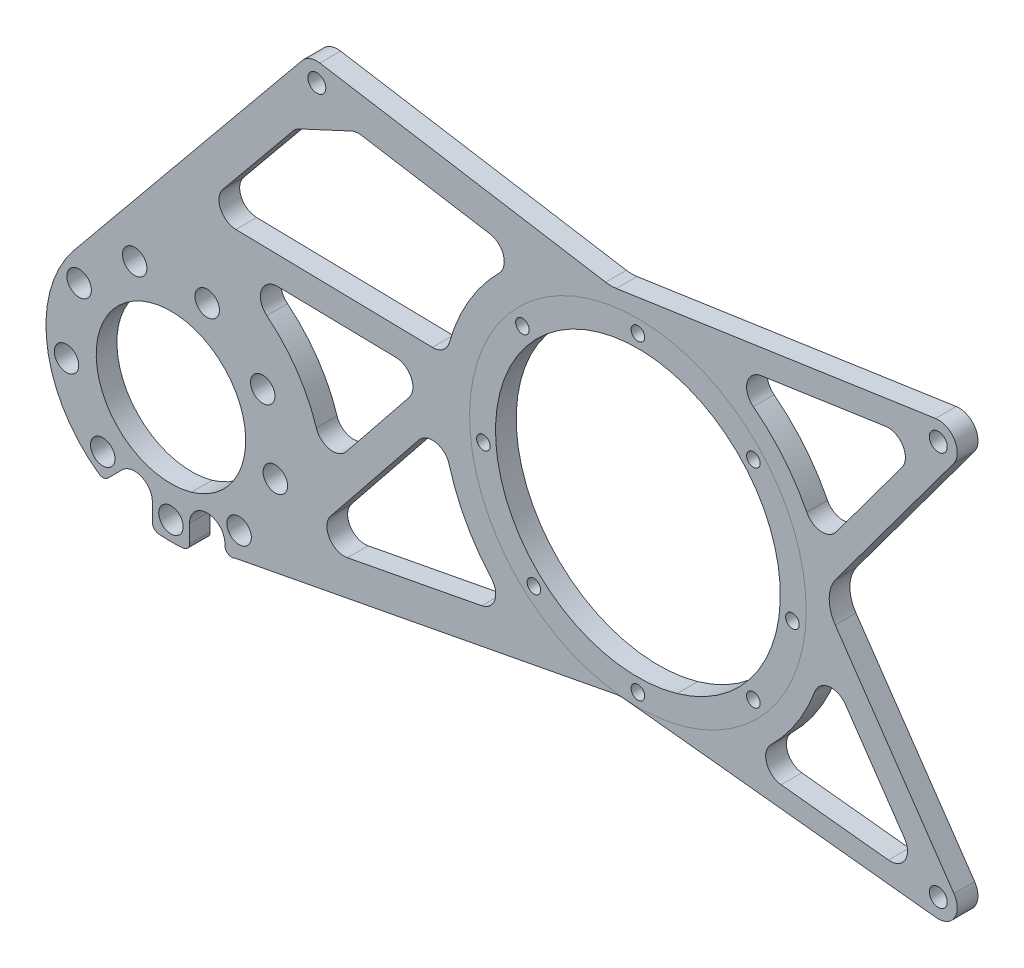
SolidWorks part; units mm, degrees
material "6061-T6 (SS)"
ref_plane "X-Y Datum" through (0, 0, 0) normal (0, 0, 1) x (1, 0, 0)
ref_plane "X-Z Datum" through (0, 0, 0) normal (0, 1, 0) x (1, 0, 0)
ref_plane "Y-Z Datum" through (0, 0, 0) normal (1, 0, 0) x (0, 0, -1)
sketch "Sketch15" plane through (0, 0, 0) normal (0, 0, 1) x (-1, 0, 0)
  line L0 (-666.75, 77.9015) -> (-548.64, 0) construction
  line L1 (-666.75, 77.9015) -> (-494.9785, 127) construction
  line L8 (-471.7786, 164.3167) -> (-477.0435, 159.0518)
  line L9 (-488.1397, 163.648) -> (-488.1397, 170.2207)
  line L10 (-501.8173, 170.2207) -> (-501.8173, 163.648)
  line L11 (-514.8173, 163.648) -> (-514.8173, 164.225)
  line L17 (-660.4, 0) -> (-548.64, 0)
  line L18 (-777.24, 0) -> (-660.4, 0)
  line L19 (-777.24, 145.034) -> (-777.24, 0)
  line L20 (-789.94, 132.334) -> (-764.54, 157.734)
  line L21 (-789.94, 157.734) -> (-764.54, 132.334)
  line L22 (-789.94, 132.334) -> (-764.54, 132.334)
  line L23 (-789.94, 157.734) -> (-764.54, 157.734)
  line L24 (-789.94, 157.734) -> (-789.94, 132.334)
  line L25 (-764.54, 157.734) -> (-764.54, 132.334)
  line L26 (-543.2372, -4.4272) -> (-459.4185, 97.8608)
  line L27 (-777.24, -6.985) -> (-548.64, -6.985)
  line L28 (-784.225, 0) -> (-784.225, 145.034)
  line L29 (-776.4928, 151.9789) -> (-660.1268, 139.4587)
  line L30 (-660.1268, 139.4587) -> (-518.666, 166.4019)
  circle A1 centre (-666.75, 77.9015) radius 52.3875
  circle A4 centre (-548.64, 0) radius 12.7
  circle A5 centre (-777.24, 0) radius 12.7
  arc A16 (-518.666, 166.4019) -> (-468.5208, 164.5979) centre (-494.9785, 127) ccw
  arc A17 (-468.5208, 164.5979) -> (-471.7786, 164.3167) centre (-469.9826, 162.5207) ccw
  arc A18 (-488.1397, 163.648) -> (-477.0435, 159.0518) centre (-481.6397, 163.648) ccw
  arc A19 (-488.1397, 170.2207) -> (-490.4283, 172.7483) centre (-490.6797, 170.2207) ccw
  arc A20 (-490.4283, 172.7483) -> (-499.5287, 172.7483) centre (-494.9785, 127) ccw
  arc A21 (-499.5287, 172.7483) -> (-501.8173, 170.2207) centre (-499.2773, 170.2207) ccw
  arc A22 (-514.8173, 163.648) -> (-501.8173, 163.648) centre (-508.3173, 163.648) ccw
  arc A23 (-514.8173, 164.225) -> (-518.666, 166.4019) centre (-517.3573, 164.225) ccw
  circle A30 centre (-709.2207, 116.1423) radius 2.5
  circle A31 centre (-624.2793, 39.6607) radius 2.5
  circle A33 centre (-709.2207, 39.6607) radius 2.5
  circle A34 centre (-723.5869, 83.8753) radius 2.5
  circle A35 centre (-609.9131, 83.8753) radius 2.5
  circle A36 centre (-666.75, 20.7515) radius 2.5
  arc A40 (-666.75, 132.5515) -> (-666.75, 137.5515) centre (-666.75, 135.0515) ccw
  arc A41 (-666.75, 137.5515) -> (-666.75, 132.5515) centre (-666.75, 135.0515) ccw
  circle A43 centre (-628.5092, 120.3722) radius 2.5
  circle A45 centre (-666.75, 77.9015) radius 61.9125
  circle A46 centre (-548.64, 0) radius 3.3
  circle A47 centre (-777.24, 0) radius 3.3
  circle A48 centre (-777.24, 145.034) radius 3.3
  circle A49 centre (-548.64, 0) radius 6.985
  circle A50 centre (-777.24, 0) radius 6.985
  circle A51 centre (-777.24, 145.034) radius 6.985
  circle A61 centre (-461.2035, 107.5) radius 4.5
  circle A62 centre (-481.6397, 90.352) radius 4.5
  circle A63 centre (-508.3173, 90.352) radius 4.5
  circle A64 centre (-528.7535, 107.5) radius 4.5
  circle A65 centre (-533.386, 133.7723) radius 4.5
  circle A66 centre (-520.0472, 156.8757) radius 4.5
  circle A67 centre (-494.9785, 166) radius 4.5
  circle A68 centre (-469.9098, 156.8757) radius 4.5
  circle A69 centre (-456.571, 133.7723) radius 4.5
  circle A71 centre (-494.9785, 127) radius 27.4955
  dimension "D2" = 6.6
  dimension "D3" = 6.6
  dimension "D4" = 6.6
  dimension "D5" = 13.97
  dimension "D6" = 13.97
  dimension "D7" = 13.97
  dimension "D1" = 141.4871
extrude "Boss-Extrude1" add sketch "Sketch15" along normal blind 7.62 contours A45 A1 A30 A31 A33 A34 A35 A36 A41 A40 A43 | L30 A45 L29 L25 L22 L19 A5 L18 L17 A4 L26 A16 | A51 L21 L25 L29 L20 | A51 L19 L22 L21 | L19 A51 L21 A48 | L20 A51 L19 A48 | A51 L28 L20 | A51 L20 L28 L22 L19 | L21 A51 L20 A48 | A51 L20 A48 L21 | L20 A51 L21 A48 | A51 L20 L29 | A5 L19 L22 L28 | A50 L19 A5 L28 | A50 L18 A5 L19 | A50 L27 A5 L18 | A50 L18 A47 L19 | L18 A50 L19 A47 | A5 L27 A4 L17 L18 | A49 L17 A4 L27 | A49 L26 A4 L17 | A49 A46 | L11 A23 A16 A17 L8 A18 L9 A19 A20 A21 L10 A22 A71 A69 A68 A67 A66 A65 A64 A63 A62 A61 region at (470.0892, -163.7557, 0) region at (621.9919, -118.1022, 0) region at (500.7414, -53.0926, 0) region at (540.1092, 0.1341, 0) region at (545.7357, 6.1347, 0) region at (662.94, 3.5042, 0) region at (557.2397, 3.7525, 0) region at (767.6155, -143.202, 0) region at (768.6403, 3.7525, 0) region at (770.798, -6.442, 0) region at (772.2286, -135.2354, 0) region at (772.7928, -151.1055, 0) region at (782.0394, 4.7994, 0) region at (780.9925, -8.5997, 0) region at (780.7424, -72.1789, 0) region at (773.8261, -3.4139, 0) region at (775.2402, -140.206, 0) region at (772.412, -145.034, 0) region at (780.8486, -135.5958, 0) region at (777.24, -149.862, 0) region at (782.068, -145.034, 0) region at (779.2398, -140.206, 0) region at (783.5955, -140.54, 0)
ref_point "Point1"
ref_point "Point2"
ref_plane "Plane1" through (666.75, -77.9015, 0) normal (-0.9615, -0.2748, 0) x (0, 0, 1)
ref_plane "Plane2" through (494.9785, -127, 0) normal (0.9615, 0.2748, 0) x (0, 0, -1)
split line "Split Line1"
split line "Split Line2"
sketch "Sketch17" plane through (0, 0, 7.62) normal (0, 0, 1) x (1, 0, 0)
  circle A0 centre (666.75, -77.9015) radius 61.9125 construction
  circle A1 centre (666.75, -77.9015) radius 61.9125
split line "Split Line3"
ref_axis "Axis4" through (666.75, -77.9015, 7.62) along (0, 0, -1)
ref_axis "Axis5" through (494.9785, -127, 7.62) along (0, 0, -1)
sketch "Sketch18" plane through (0, 0, 7.62) normal (0, 0, 1) x (1, 0, 0)
  line L4 (514.8173, -163.648) -> (514.8173, -164.225)
  line L5 (501.8173, -170.2207) -> (501.8173, -163.648)
  line L6 (488.1397, -163.648) -> (488.1397, -170.2207)
  line L7 (471.7786, -164.3167) -> (477.0435, -159.0518)
  line L8 (514.8173, -163.648) -> (514.8173, -164.225)
  line L9 (501.8173, -170.2207) -> (501.8173, -163.648)
  line L10 (488.1397, -163.648) -> (488.1397, -170.2207)
  line L11 (471.7786, -164.3167) -> (477.0435, -159.0518)
  line L12 (734.2162, -69.8493) -> (782.8538, -4.1564)
  line L13 (734.2162, -69.8493) -> (783.0031, -141.0872)
  line L14 (776.2216, 6.9104) -> (656.8438, -10.6825)
  line L15 (656.8438, -10.6825) -> (549.7714, 6.8928)
  line L16 (776.4928, -151.9789) -> (687.9549, -142.4528)
  line L17 (776.4928, -151.9789) -> (660.1268, -139.4587) construction
  line L18 (543.2372, 4.4272) -> (459.4185, -97.8608) construction
  line L19 (543.2372, 4.4272) -> (459.4185, -97.8608)
  line L20 (660.1268, -139.4587) -> (518.666, -166.4019) construction
  line L21 (660.1268, -139.4587) -> (518.666, -166.4019)
  circle A0 centre (666.75, -77.9015) radius 67.945
  circle A1 centre (666.75, -77.9015) radius 52.3875
  circle A2 centre (666.75, -77.9015) radius 52.3875
  circle A3 centre (548.64, 0) radius 12.7
  circle A4 centre (548.64, 0) radius 12.7
  circle A5 centre (777.24, 0) radius 12.7
  circle A6 centre (777.24, 0) radius 12.7
  circle A7 centre (777.24, 0) radius 6.985 construction
  circle A8 centre (777.24, -145.034) radius 6.985 construction
  circle A9 centre (548.64, 0) radius 6.985 construction
  arc A10 (514.8173, -164.225) -> (518.666, -166.4019) centre (517.3573, -164.225) ccw
  arc A11 (514.8173, -163.648) -> (501.8173, -163.648) centre (508.3173, -163.648) ccw
  arc A12 (499.5287, -172.7483) -> (501.8173, -170.2207) centre (499.2773, -170.2207) ccw
  arc A13 (490.4283, -172.7483) -> (499.5287, -172.7483) centre (494.9785, -127) ccw
  arc A14 (488.1397, -170.2207) -> (490.4283, -172.7483) centre (490.6797, -170.2207) ccw
  arc A15 (488.1397, -163.648) -> (477.0435, -159.0518) centre (481.6397, -163.648) ccw
  arc A16 (468.5208, -164.5979) -> (471.7786, -164.3167) centre (469.9826, -162.5207) ccw
  arc A17 (518.666, -166.4019) -> (468.5208, -164.5979) centre (494.9785, -127) ccw
  arc A18 (514.8173, -164.225) -> (518.666, -166.4019) centre (517.3573, -164.225) ccw
  arc A19 (514.8173, -163.648) -> (501.8173, -163.648) centre (508.3173, -163.648) ccw
  arc A20 (499.5287, -172.7483) -> (501.8173, -170.2207) centre (499.2773, -170.2207) ccw
  arc A21 (490.4283, -172.7483) -> (499.5287, -172.7483) centre (494.9785, -127) ccw
  arc A22 (488.1397, -170.2207) -> (490.4283, -172.7483) centre (490.6797, -170.2207) ccw
  arc A23 (488.1397, -163.648) -> (477.0435, -159.0518) centre (481.6397, -163.648) ccw
  arc A24 (468.5208, -164.5979) -> (471.7786, -164.3167) centre (469.9826, -162.5207) ccw
  arc A25 (518.666, -166.4019) -> (468.5208, -164.5979) centre (494.9785, -127) ccw
  circle A26 centre (777.24, -145.034) radius 6.985
  circle A27 centre (777.24, 0) radius 6.985
  circle A28 centre (548.64, 0) radius 6.985
  line M37 (784.225, -145.034) -> (784.225, 0)
  line M39 (777.24, 6.985) -> (548.64, 6.985)
  dimension "D5" = 135.89
  dimension "D6" = 65.6929
  dimension "D1" = 0
  dimension "D2" = 0
  dimension "D3" = 0
  dimension "D4" = 0
extrude "Profile" cut sketch "Sketch18" against normal through all contours A6 A4 L15 L14 M39 | A28 L15 A4 M39 | A27 A6 L14 M39 | A26 A6 L12 L13 M37 | A27 L12 A6 M37 region at (660.9586, 1.0495, 7.62) region at (769.684, 6.4437, 7.62) region at (556.2469, 6.3803, 7.62) region at (767.4156, -72.3216, 7.62) region at (781.5837, -8.7535, 7.62)
fillet "Prof Fillet" radius 12.7 3 edges at (660.1268, -139.4587, 3.81) (734.2162, -69.8493, 3.81) (656.8438, -10.6825, 3.81)
sketch "Sketch19" plane through (0, 0, 7.62) normal (0, 0, 1) x (1, 0, 0)
  line L0 (732.9468, -56.6236) -> (772.9791, -2.5535)
  line L1 (772.9791, -2.5535) -> (694.453, -14.126)
  line L2 (776.2216, 6.9104) -> (658.8007, -10.3941) construction
  line L3 (739.5986, -62.5794) -> (782.8538, -4.1564) construction
  line L4 (514.8173, -163.648) -> (514.8173, -164.225)
  line L5 (501.8173, -170.2207) -> (501.8173, -163.648)
  line L6 (488.1397, -163.648) -> (488.1397, -170.2207)
  line L7 (471.7786, -164.3167) -> (477.0435, -159.0518)
  line L8 (514.8173, -163.648) -> (514.8173, -164.225)
  line L9 (501.8173, -170.2207) -> (501.8173, -163.648)
  line L10 (488.1397, -163.648) -> (488.1397, -170.2207)
  line L11 (471.7786, -164.3167) -> (477.0435, -159.0518)
  line L12 (735.3185, -89.4398) -> (772.6135, -143.8976)
  line L13 (772.6135, -143.8976) -> (704.1334, -136.5295)
  line L14 (739.3273, -77.3124) -> (783.0031, -141.0872) construction
  line L15 (776.4928, -151.9789) -> (660.1268, -139.4587) construction
  arc A0 (694.453, -14.126) -> (732.9468, -56.6236) centre (666.75, -77.9015) cw
  circle A1 centre (666.75, -77.9015) radius 52.3875
  circle A2 centre (666.75, -77.9015) radius 52.3875
  circle A3 centre (548.64, 0) radius 12.7
  circle A4 centre (548.64, 0) radius 12.7
  circle A5 centre (777.24, 0) radius 12.7
  circle A6 centre (777.24, 0) radius 12.7
  circle A7 centre (666.75, -77.9015) radius 61.9125 construction
  arc A8 (704.1334, -136.5295) -> (735.3185, -89.4398) centre (666.75, -77.9015) ccw
  arc A10 (514.8173, -164.225) -> (518.666, -166.4019) centre (517.3573, -164.225) ccw
  arc A11 (514.8173, -163.648) -> (501.8173, -163.648) centre (508.3173, -163.648) ccw
  arc A12 (499.5287, -172.7483) -> (501.8173, -170.2207) centre (499.2773, -170.2207) ccw
  arc A13 (490.4283, -172.7483) -> (499.5287, -172.7483) centre (494.9785, -127) ccw
  arc A14 (488.1397, -170.2207) -> (490.4283, -172.7483) centre (490.6797, -170.2207) ccw
  arc A15 (488.1397, -163.648) -> (477.0435, -159.0518) centre (481.6397, -163.648) ccw
  arc A16 (468.5208, -164.5979) -> (471.7786, -164.3167) centre (469.9826, -162.5207) ccw
  arc A17 (518.666, -166.4019) -> (468.5208, -164.5979) centre (494.9785, -127) ccw
  arc A18 (514.8173, -164.225) -> (518.666, -166.4019) centre (517.3573, -164.225) ccw
  arc A19 (514.8173, -163.648) -> (501.8173, -163.648) centre (508.3173, -163.648) ccw
  arc A20 (499.5287, -172.7483) -> (501.8173, -170.2207) centre (499.2773, -170.2207) ccw
  arc A21 (490.4283, -172.7483) -> (499.5287, -172.7483) centre (494.9785, -127) ccw
  arc A22 (488.1397, -170.2207) -> (490.4283, -172.7483) centre (490.6797, -170.2207) ccw
  arc A23 (488.1397, -163.648) -> (477.0435, -159.0518) centre (481.6397, -163.648) ccw
  arc A24 (468.5208, -164.5979) -> (471.7786, -164.3167) centre (469.9826, -162.5207) ccw
  arc A25 (518.666, -166.4019) -> (468.5208, -164.5979) centre (494.9785, -127) ccw
  dimension "D7" = 7.62
  dimension "D8" = 7.62
  dimension "D5" = 8.89
  dimension "D6" = 8.89
  dimension "D9" = 10.16
  dimension "D10" = 7.62
  dimension "D1" = 0
  dimension "D2" = 0
  dimension "D3" = 0
  dimension "D4" = 0
extrude "Cut-Extrude2" cut sketch "Sketch19" against normal through all contours L1 A0 L0 | A8 L13 L12 | L1 A6 L0 | L13 A8 L12 region at (735.5667, -23.3598, 7.62) region at (768.629, -5.1605, 7.62) region at (739.7271, -124.6517, 7.62)
fillet "Fillet2" radius 6.35 6 edges at (694.453, -14.126, 3.81) (772.9791, -2.5535, 3.81) (732.9468, -56.6236, 3.81) (772.6135, -143.8976, 3.81) (704.1334, -136.5295, 3.81) (735.3185, -89.4398, 3.81)
sketch "Sketch22" plane through (0, 0, 7.62) normal (0, 0, 1) x (1, 0, 0)
  line L0 (625.9593, -18.4829) -> (563.0994, -8.1649)
  line L1 (563.0994, -8.1649) -> (540.883, -18.4829)
  line L2 (654.892, -10.3621) -> (549.7714, 6.8928) construction
  line L4 (514.8173, -163.648) -> (514.8173, -164.225)
  line L5 (501.8173, -170.2207) -> (501.8173, -163.648)
  line L6 (488.1397, -163.648) -> (488.1397, -170.2207)
  line L7 (471.7786, -164.3167) -> (477.0435, -159.0518)
  line L8 (514.8173, -163.648) -> (514.8173, -164.225)
  line L9 (501.8173, -170.2207) -> (501.8173, -163.648)
  line L10 (488.1397, -163.648) -> (488.1397, -170.2207)
  line L11 (471.7786, -164.3167) -> (477.0435, -159.0518)
  line L12 (621.3887, -133.9086) -> (542.9827, -148.8422)
  line L13 (542.9827, -148.8422) -> (594.9409, -84.0572)
  line L14 (658.2707, -139.8122) -> (518.666, -166.4019) construction
  line L15 (505.7956, -61.3018) -> (540.883, -18.4829)
  line L16 (540.883, -18.4829) -> (625.9593, -18.4829)
  line L17 (596.2144, -63.0967) -> (505.7956, -61.3018)
  line L18 (543.2372, 4.4272) -> (459.4185, -97.8608) construction
  line L19 (502.7234, -71.4029) -> (590.6658, -73.1486)
  line L20 (590.6658, -73.1486) -> (550.9456, -122.6744)
  arc A0 (594.9409, -84.0572) -> (621.3887, -133.9086) centre (666.75, -77.9015) ccw
  circle A1 centre (666.75, -77.9015) radius 52.3875
  circle A2 centre (666.75, -77.9015) radius 52.3875
  circle A3 centre (548.64, 0) radius 12.7
  circle A4 centre (548.64, 0) radius 12.7
  circle A5 centre (777.24, 0) radius 12.7
  circle A6 centre (777.24, 0) radius 12.7
  circle A7 centre (666.75, -77.9015) radius 61.9125 construction
  arc A8 (625.9593, -18.4829) -> (596.2144, -63.0967) centre (666.75, -77.9015) ccw
  arc A9 (502.7234, -71.4029) -> (550.9456, -122.6744) centre (494.9785, -127) cw
  arc A10 (514.8173, -164.225) -> (518.666, -166.4019) centre (517.3573, -164.225) ccw
  arc A11 (514.8173, -163.648) -> (501.8173, -163.648) centre (508.3173, -163.648) ccw
  arc A12 (499.5287, -172.7483) -> (501.8173, -170.2207) centre (499.2773, -170.2207) ccw
  arc A13 (490.4283, -172.7483) -> (499.5287, -172.7483) centre (494.9785, -127) ccw
  arc A14 (488.1397, -170.2207) -> (490.4283, -172.7483) centre (490.6797, -170.2207) ccw
  arc A15 (488.1397, -163.648) -> (477.0435, -159.0518) centre (481.6397, -163.648) ccw
  arc A16 (468.5208, -164.5979) -> (471.7786, -164.3167) centre (469.9826, -162.5207) ccw
  arc A17 (518.666, -166.4019) -> (468.5208, -164.5979) centre (494.9785, -127) ccw
  arc A18 (514.8173, -164.225) -> (518.666, -166.4019) centre (517.3573, -164.225) ccw
  arc A19 (514.8173, -163.648) -> (501.8173, -163.648) centre (508.3173, -163.648) ccw
  arc A20 (499.5287, -172.7483) -> (501.8173, -170.2207) centre (499.2773, -170.2207) ccw
  arc A21 (490.4283, -172.7483) -> (499.5287, -172.7483) centre (494.9785, -127) ccw
  arc A22 (488.1397, -170.2207) -> (490.4283, -172.7483) centre (490.6797, -170.2207) ccw
  arc A23 (488.1397, -163.648) -> (477.0435, -159.0518) centre (481.6397, -163.648) ccw
  arc A24 (468.5208, -164.5979) -> (471.7786, -164.3167) centre (469.9826, -162.5207) ccw
  arc A25 (518.666, -166.4019) -> (468.5208, -164.5979) centre (494.9785, -127) ccw
  dimension "D6" = 10.16
  dimension "D7" = 10.16
  dimension "D14" = 10.16
  dimension "D5" = 12.7
  dimension "D8" = 12.7
  dimension "D9" = 12.7
  dimension "D10" = 24.4955
  dimension "D11" = 90.4189
  dimension "D12" = 51.9581
  dimension "D13" = 64.7849
  dimension "D15" = 10.16
  dimension "D16" = 10.16
  dimension "D17" = 1.7949
  dimension "D1" = 0
  dimension "D2" = 0
  dimension "D3" = 0
  dimension "D4" = 0
extrude "Cut-Extrude4" cut sketch "Sketch22" against normal through all contours L1 L16 L0 | L17 L15 L16 A8 | L20 A9 L19 | L13 A0 L12 region at (576.6473, -15.0436, 7.62)
fillet "Fillet5" radius 6.35 11 edges at (621.3887, -133.9086, 3.81) (542.9827, -148.8422, 3.81) (594.9409, -84.0572, 3.81) (550.9456, -122.6744, 3.81) (590.6658, -73.1486, 3.81) (502.7234, -71.4029, 3.81) (596.2144, -63.0967, 3.81) (505.7956, -61.3018, 3.81) (625.9593, -18.4829, 3.81) (563.0994, -8.1649, 3.81) (540.883, -18.4829, 3.81)
